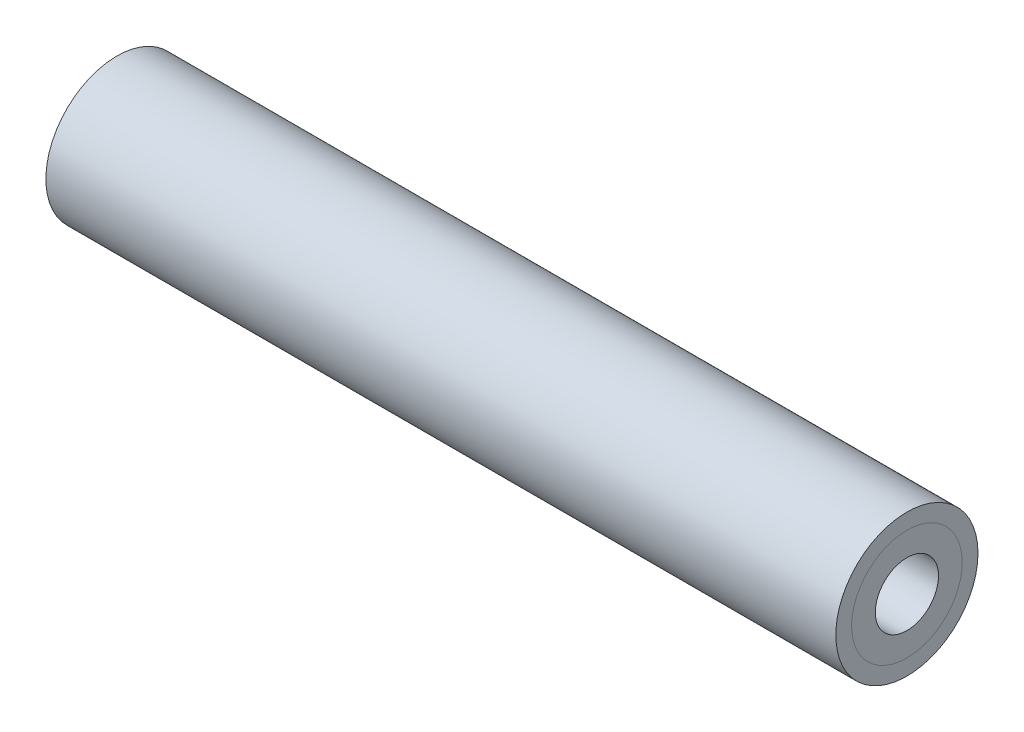
SolidWorks part; units mm, degrees
note: The reader was unsure of these and kept them because the rebuilt part matched: shared geometry of "Sketch3<2>".
ref_plane "Front Plane" through (0, 0, 0) normal (0, 0, 1) x (1, 0, 0)
ref_plane "Top Plane" through (0, 0, 0) normal (0, 1, 0) x (1, 0, 0)
ref_plane "Right Plane" through (0, 0, 0) normal (1, 0, 0) x (0, 0, -1)
sketch "Sketch1" plane through (0, 0, 0) normal (1, 0, 0) x (0, 0, -1)
  circle A0 centre (0, 0) radius 9
  circle A1 centre (0, 0) radius 7
  dimension "D1" = 18
  dimension "D2" = 2
extrude "Boss-Extrude1" add sketch "Sketch1" along normal mid plane 100
sketch "Sketch3" plane through (50, 0, 0) normal (1, 0, 0) x (0, 0, -1)
  circle A0 centre (0, 0) radius 7 construction
  circle A1 centre (0, 0) radius 7
  circle A2 centre (0, 0) radius 4
  dimension "D1" = 8
extrude "Boss-Extrude3" add sketch "Sketch3" against normal blind 15 separate body
extrude "Boss-Extrude4" add sketch "Sketch3<2>" along normal blind 15 from offset 100 separate body
sketch "Sketch3<2>" plane through (50, 0, 0) normal (1, 0, 0) x (0, 0, -1) same geometry as "Sketch3"
